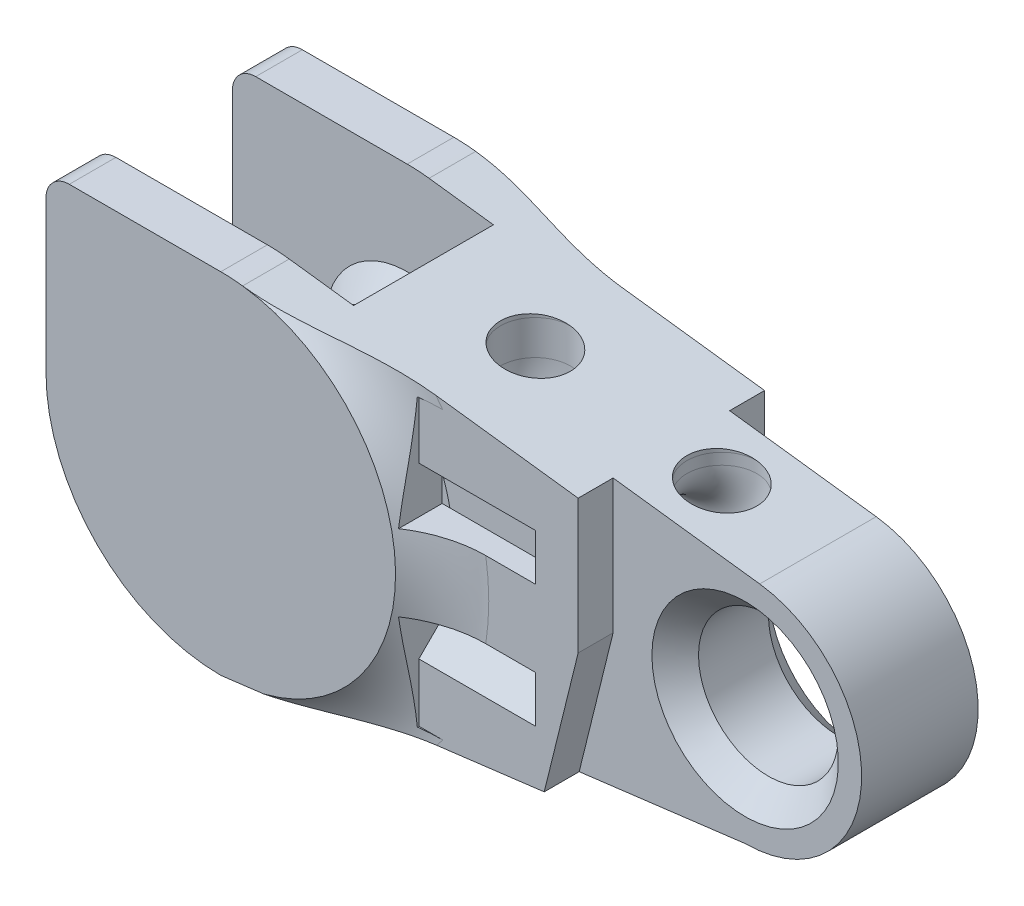
SolidWorks part; units mm, degrees
ref_plane "Front Plane" through (0, 0, 0) normal (0, 0, 1) x (1, 0, 0)
ref_plane "Top Plane" through (0, 0, 0) normal (0, 1, 0) x (1, 0, 0)
ref_plane "Right Plane" through (0, 0, 0) normal (1, 0, 0) x (0, 0, -1)
sketch "Sketch1" plane through (0, 0, 0) normal (0, 0, 1) x (1, 0, 0)
  line L0 (55, 0) -> (-55, 0) construction
  line L1 (0, -55) -> (0, 55) construction
  line L2 (-9.0625, 7.4412) -> (10.625, 4.9608)
  line L3 (-10, -7.5) -> (10, -5)
  line L4 (-10, 7.5) -> (-16.5, 7.5)
  line L5 (-17.5, 6.5) -> (-17.5, 0)
  arc A0 (-17.5, 0) -> (-10, 7.5) centre (-10, 0) ccw
  circle A1 centre (10, 0) radius 5
  circle A2 centre (-10, 0) radius 2.5
  circle A3 centre (10, 0) radius 3
  arc A4 (-17.5, 6.5) -> (-16.5, 7.5) centre (-16.5, 6.5) cw
  dimension "D1" = 15
  dimension "D2" = 10
  dimension "D5" = 5
  dimension "D6" = 6
  dimension "D7" = 1
  dimension "D3" = 20
  dimension "D4" = 10
extrude "Boss-Extrude1" add sketch "Sketch1" along normal mid plane 8 contours A1 L2 A0 L3 region at (1.0148, 0.0458, 0)
extrude "Boss-Extrude2" add sketch "Sketch1<3>" along normal mid plane 10 contours A0 L3 A2 region at (-2.726, 0.4493, 0)
sketch "Sketch1<3>" plane through (0, 0, 0) normal (0, 0, 1) x (1, 0, 0) same geometry as "Sketch1"
extrude "Boss-Extrude3" add sketch "Sketch1<5>" along normal mid plane 9 contours A1 A3 region at (13.6439, 3.2136, 0)
sketch "Sketch1<5>" plane through (0, 0, 0) normal (0, 0, 1) x (1, 0, 0) same geometry as "Sketch1"
fillet "Fillet1" radius 5 2 edges at (-2.5143, 0.4624, -4) (-2.5143, 0.4624, 4)
sketch "Sketch2" plane through (0, 0, 0) normal (0, 0, 1) x (1, 0, 0)
  line L0 (-2, 0) -> (-2, -8)
  line L1 (-2, -8) -> (-10, -8)
  line L2 (4.3346, 0) -> (2, -9.4488)
  line L3 (2, -9.4488) -> (10, -9.4488)
  line L4 (10, -9.4488) -> (10, -5.5)
  line L5 (4.3346, 0) -> (4.3346, 6.1306)
  line L6 (55, 0) -> (-55, 0) construction
  line L7 (4.3346, 6.1306) -> (10, 5.5)
  line L8 (-18, 0) -> (-18, 8.1082)
  line L9 (-18, 8.1082) -> (-10, 8)
  arc A0 (-2, 0) -> (-10, 8) centre (-10, 0) ccw
  arc A1 (10, -5.5) -> (10, 5.5) centre (10, 0) ccw
  arc A2 (-18, 0) -> (-10, -8) centre (-10, 0) ccw
  dimension "D1" = 16
  dimension "D2" = 11
  dimension "D3" = 8
extrude "Cut-Extrude3" cut sketch "Sketch2" against normal mid plane 6 contours L0 A0 L1 region at (-10.0101, 0.0152, 0)
extrude "Cut-Extrude4" cut sketch "Sketch2<3>" along normal blind 7.5 from offset 10 contours A1 region at (8.574, -1.5618, 0) offset against normal yes
sketch "Sketch2<3>" plane through (0, 0, 0) normal (0, 0, 1) x (1, 0, 0) same geometry as "Sketch2"
mirror "Mirror1" about plane through (0, 0, 0) normal (0, 0, 1) of "Cut-Extrude4"
sketch "Sketch3" plane through (0, 0, 0) normal (0, 0, 1) x (1, 0, 0)
  line L0 (-1.5, 6.4884) -> (-1.5, 5)
  line L1 (-1.7717, 6.5226) -> (-9.0625, 7.4412) construction
  line L2 (1.5, 2) -> (3.5, 2)
  line L3 (6.5, 5) -> (6.5, 5.4805)
  line L4 (-1.7717, 6.5226) -> (4.3346, 5.7533) construction
  line L5 (-1.5, 6.4884) -> (-1.5, 8.192)
  line L6 (6.5, 5.4805) -> (6.5, 8.192)
  line L8 (0, -55) -> (0, 55) construction
  line L9 (55, 0) -> (-55, 0) construction
  arc A2 (6.5, 5) -> (3.5, 2) centre (3.5, 5) cw
  arc A3 (1.5, 2) -> (-1.5, 5) centre (1.5, 5) cw
  point P24 (6.5, 2)
  point P27 (-1.5, 2)
  dimension "D1" = 8
  dimension "D2" = 1.5
  dimension "D3" = 2
sweep "Cut-Sweep5" cut path "Sketch3" circular profile diameter 3 parameters "D3"=3
mirror "Mirror4" about plane through (0, 0, 0) normal (0, 1, 0) of "Cut-Sweep5"
extrude "Boss-Extrude4" add sketch "Sketch1<7>" along normal mid plane 10 contours A2 region at (-10, 0, 0)
sketch "Sketch1<7>" plane through (0, 0, 0) normal (0, 0, 1) x (1, 0, 0) same geometry as "Sketch1"
chamfer "Chamfer2" distance 1 angle 45 4 edges at (13, 0, -2.5) (7, 0, 2.5) (-7.5, 0, 3) (-7.5, 0, -3)
sketch "Sketch85" plane through (0, 0, 0) normal (1, 0, 0) x (0, 0, -1)
  line L0 (4, -6.4659) -> (4, 6.5226) construction
  line L1 (4, 6.138) -> (4, 3.638)
  line L2 (4, 6.5226) -> (4, 5.7533) construction
  line L3 (4, 3.638) -> (3, 2.638)
  line L4 (3, 2.638) -> (3, 1.638)
  line L5 (3, 1.638) -> (5.3407, 1.638)
  line L6 (5.3407, 1.638) -> (5.3407, 6.138)
  line L7 (5.3407, 6.138) -> (4, 6.138)
  line L8 (4, 5.7533) -> (4, 0) construction
  dimension "D1" = 2.5
  dimension "D2" = 1
  dimension "D3" = 1
  dimension "D4" = 1
extrude "Cut-Extrude5" cut sketch "Sketch85" against normal mid plane 5
mirror "Mirror5" about plane through (0, 0, 0) normal (0, 1, 0) of "Cut-Extrude5"
mirror "Mirror6" about plane through (0, 0, 0) normal (0, 0, 1) of "Mirror5"
